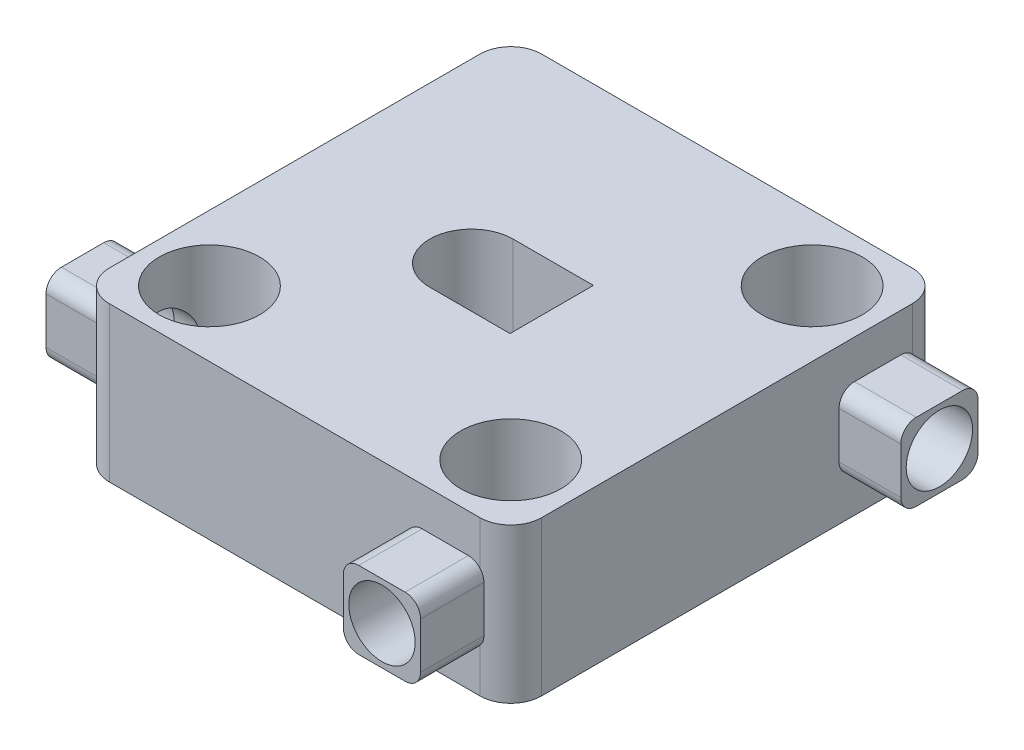
SolidWorks part; units mm, degrees
ref_plane "Front Plane" through (0, 0, 0) normal (0, 0, 1) x (1, 0, 0)
ref_plane "Top Plane" through (0, 0, 0) normal (0, 1, 0) x (1, 0, 0)
ref_plane "Right Plane" through (0, 0, 0) normal (1, 0, 0) x (0, 0, -1)
sketch "Sketch1" plane through (0, 0, 0) normal (0, 1, 0) x (1, 0, 0)
  line L0 (0.9332, 0.6825) -> (28.9332, 0.6825)
  line L1 (0.9332, 0.6825) -> (0.9332, 28.6825)
  line L2 (0.9332, 28.6825) -> (28.9332, 28.6825)
  line L3 (28.9332, 0.6825) -> (28.9332, 28.6825)
  line L4 (17.3832, 17.1825) -> (17.3832, 12.1825) construction
  line L5 (17.3832, 12.1825) -> (12.3832, 12.1825) construction
  line L6 (17.3832, 17.1825) -> (12.3832, 17.1825) construction
  line L7 (0.9332, 0.6825) -> (5.1758, 4.9251) construction
  line L8 (5.1758, 4.9251) -> (24.6905, 24.4399) construction
  line L9 (24.6905, 24.4399) -> (28.9332, 28.6825) construction
  line L10 (24.6905, 24.4399) -> (24.6905, 4.9251) construction
  line L11 (24.6905, 4.9251) -> (5.1758, 4.9251) construction
  line L12 (17.5832, 17.3825) -> (17.5832, 11.9825)
  line L13 (17.5832, 11.9825) -> (12.3832, 11.9825)
  line L14 (17.5832, 17.3825) -> (12.3832, 17.3825)
  line L15 (12.3832, 14.6825) -> (12.3832, 12.1325) construction
  circle A0 centre (5.1758, 4.9251) radius 3.25
  circle A1 centre (24.6905, 4.9251) radius 3.25
  circle A2 centre (24.6905, 24.4399) radius 3.25
  arc A3 (12.3832, 17.1825) -> (12.3832, 12.1825) centre (12.3832, 14.6825) ccw construction
  arc A4 (12.3832, 17.3825) -> (12.3832, 11.9825) centre (12.3832, 14.6825) ccw
  dimension "D2" = 6.5
  dimension "D6" = 5
  dimension "D1" = 28
  dimension "D3" = 6
  dimension "D4" = 2.55
  dimension "D5" = 5
  dimension "D7" = 11.45
  dimension "D8" = 0.2
extrude "Boss-Extrude1" add sketch "Sketch1" along normal blind 10
fillet "Fillet1" radius 2 4 edges at (0.9332, 5, -0.6825) (0.9332, 5, -28.6825) (28.9332, 5, -28.6825) (28.9332, 5, -0.6825)
sketch "Sketch2" plane through (28.9332, 0, 0) normal (1, 0, 0) x (0, 0, -1)
  line L1 (21.9399, 2.5) -> (26.9399, 2.5)
  line L2 (21.9399, 2.5) -> (21.9399, 7.5)
  line L3 (21.9399, 7.5) -> (26.9399, 7.5)
  line L4 (26.9399, 2.5) -> (26.9399, 7.5)
  line L5 (21.9399, 2.5) -> (26.9399, 7.5) construction
  line L6 (21.9399, 7.5) -> (26.9399, 2.5) construction
  line L8 (26.6825, 5) -> (24.4399, 5) construction
  line L9 (26.6825, 0) -> (26.6825, 10) construction
  line L10 (24.4399, 5) -> (24.4399, 0) construction
  line L11 (21.1899, 0) -> (27.6899, 0) construction
  circle A0 centre (24.4399, 5) radius 2.15
  circle A1 centre (24.4399, 5) radius 1.95
  point P0 (24.4399, 5)
  point P14 (26.136, 7.5)
  dimension "D1" = 4.3
  dimension "D2" = 3.9
  dimension "D3" = 5
extrude "Boss-Extrude2" add sketch "Sketch2" along normal blind 4 and the other way blind 0.5 contours L3 L4 L1 L2
extrude "Cut-Extrude1" cut sketch "Sketch2<3>" against normal blind 4 and the other way blind 5 contours A1
sketch "Sketch2<3>" plane through (28.9332, 0, 0) normal (1, 0, 0) x (0, 0, -1) same geometry as "Sketch2"
extrude "Cut-Extrude2" cut sketch "Sketch2<4>" against normal blind 0.5 from surface contours A0 starting at face at (32.9332, 5, -22.4899)
sketch "Sketch2<4>" plane through (28.9332, 0, 0) normal (1, 0, 0) x (0, 0, -1) same geometry as "Sketch2"
extrude "Cut-Extrude3" cut sketch "Sketch2<5>" against normal blind 4.1 from surface contours A0 starting at face at (32.9332, 5, -22.2899)
sketch "Sketch2<5>" plane through (28.9332, 0, 0) normal (1, 0, 0) x (0, 0, -1) same geometry as "Sketch2"
sketch "Sketch6" plane through (0.9332, 0, 0) normal (-1, 0, 0) x (0, 0, 1)
  line L0 (-7.4251, 2.5) -> (-2.4251, 2.5)
  line L1 (-7.4251, 2.5) -> (-7.4251, 7.5)
  line L2 (-7.4251, 7.5) -> (-2.4251, 7.5)
  line L3 (-2.4251, 2.5) -> (-2.4251, 7.5)
  line L4 (-7.4251, 2.5) -> (-2.4251, 7.5) construction
  line L5 (-7.4251, 7.5) -> (-2.4251, 2.5) construction
  line L6 (-2.6825, 5) -> (-4.9251, 5) construction
  line L7 (-4.9251, 5) -> (-4.9251, 0) construction
  line L8 (-8.1751, 0) -> (-1.6751, 0) construction
  line L9 (-2.6825, 0) -> (-2.6825, 10) construction
  circle A0 centre (-4.9251, 5) radius 2.15
  circle A1 centre (-4.9251, 5) radius 1.95
  point P0 (-4.9251, 5)
  point P10 (0, 0)
  point P13 (0, 0)
  line M9 (-2.6825, 0) -> (-2.6825, 10)
  dimension "D1" = 3.9
  dimension "D3" = 4.3
  dimension "D2" = 5
sketch "Sketch5" plane through (0, 0, -0.6825) normal (0, 0, -1) x (-1, 0, 0)
  line L0 (-27.1905, 2.5) -> (-22.1905, 2.5)
  line L1 (-27.1905, 2.5) -> (-27.1905, 7.5)
  line L2 (-27.1905, 7.5) -> (-22.1905, 7.5)
  line L3 (-22.1905, 2.5) -> (-22.1905, 7.5)
  line L4 (-27.1905, 2.5) -> (-22.1905, 7.5) construction
  line L5 (-27.1905, 7.5) -> (-22.1905, 2.5) construction
  line L6 (-26.9332, 5) -> (-24.6905, 5) construction
  line L7 (-24.6905, 5) -> (-24.6905, 0) construction
  line L8 (-2.9332, 0) -> (-26.9332, 0) construction
  line L9 (-26.9332, 0) -> (-26.9332, 10) construction
  line L10 (-27.9405, 0) -> (-21.4405, 0) construction
  circle A0 centre (-24.6905, 5) radius 2.15
  circle A1 centre (-24.6905, 5) radius 1.95
  point P0 (-24.6905, 5)
  point P10 (-23.851, 0)
  point P13 (-26.9332, 2.6892)
  point P16 (-26.9332, 5)
  point P19 (0, 0)
  dimension "D1" = 3.9
  dimension "D3" = 4.3
  dimension "D2" = 5
sketch "Sketch3" plane through (0, 10, 0) normal (0, 1, 0) x (1, 0, 0)
  line L0 (28.3474, 28.0967) -> (1.519, 1.2683) construction
  arc A0 (28.9332, 26.6825) -> (26.9332, 28.6825) centre (26.9332, 26.6825) ccw construction
  arc A1 (0.9332, 2.6825) -> (2.9332, 0.6825) centre (2.9332, 2.6825) ccw construction
  point P0 (28.3474, 28.0967)
  point P1 (1.519, 1.2683)
  point P10 (14.9332, 14.6825)
ref_plane "Plane1" through (0, 0, -14.6825) normal (0, 0, -1) x (-1, 0, 0)
sketch "Sketch4" plane through (0, 0, -14.6825) normal (0, 0, -1) x (-1, 0, 0)
  line L0 (-14.9332, 10) -> (-14.9332, 0) construction
  line L1 (-26.9332, 0) -> (-2.9332, 0) construction
extrude "Boss-Extrude3" add sketch "Sketch6" along normal blind 4.1 contours L2 L1 L0 A0 M9 region at (0.9332, 5, -7.3562)
extrude "Cut-Extrude4" cut sketch "Sketch6<3>" against normal blind 4.1 contours A1
sketch "Sketch6<3>" plane through (0.9332, 0, 0) normal (-1, 0, 0) x (0, 0, 1) same geometry as "Sketch6"
extrude "Boss-Extrude5" add sketch "Sketch5" against normal blind 4.1 contours A1 | A0 A1 | L2 L3 L0 L1 region at (26.7797, 5, -0.6825) region at (24.6905, 5, -0.6825)
extrude "Cut-Extrude5" cut sketch "Sketch5<4>" along normal blind 4.1 contours A1
sketch "Sketch5<4>" plane through (0, 0, -0.6825) normal (0, 0, -1) x (-1, 0, 0) same geometry as "Sketch5"
fillet "Fillet2" radius 1 12 edges at (30.9332, 7.5, -21.9399) (30.9332, 2.5, -21.9399) (30.9249, 2.5, -26.9399) (30.9249, 7.5, -26.9399) (-1.1168, 7.5, -2.6825) (-1.1168, 7.5, -7.4251) (-1.1168, 2.5, -7.4251) (-1.1168, 2.5, -2.6825) (22.1905, 7.5, 1.3675) (22.1905, 2.5, 1.3675) (27.1905, 2.5, 1.3675) (27.1905, 7.5, 1.3675)
